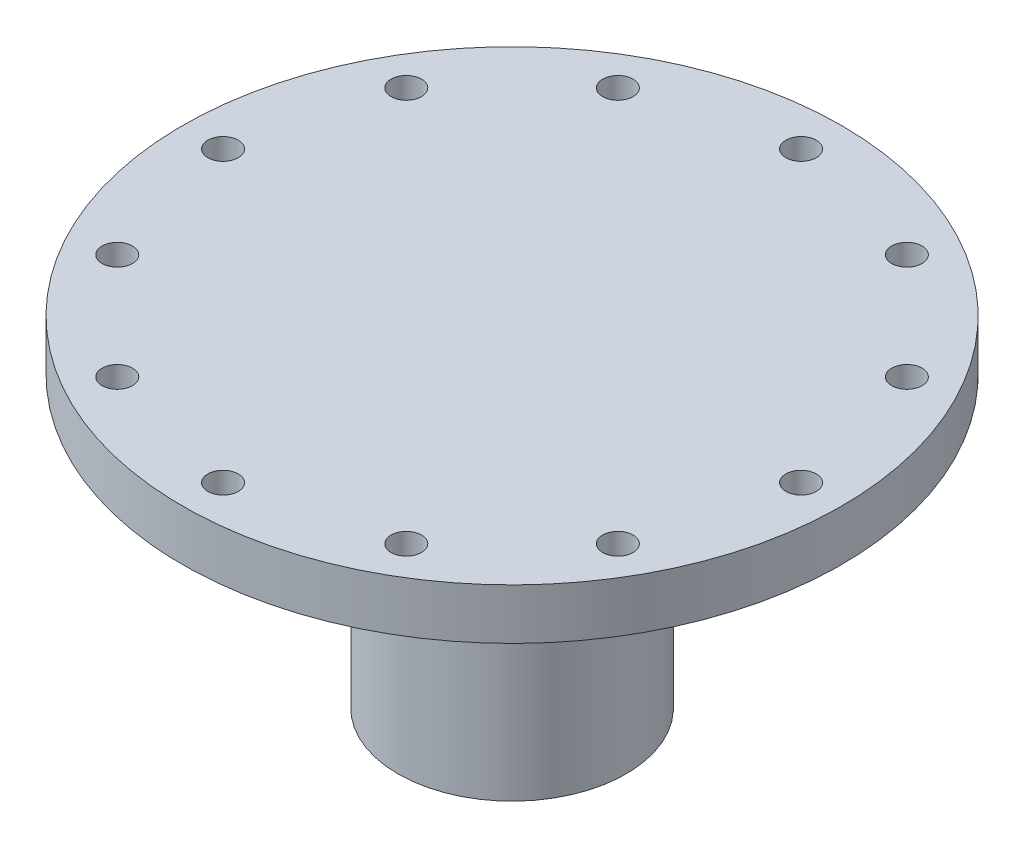
SolidWorks part; units mm, degrees
ref_plane "Front Plane" through (0, 0, 0) normal (0, 0, 1) x (1, 0, 0)
ref_plane "Top Plane" through (0, 0, 0) normal (0, 1, 0) x (1, 0, 0)
ref_plane "Right Plane" through (0, 0, 0) normal (1, 0, 0) x (0, 0, -1)
sketch "Sketch1" plane through (0, 0, 0) normal (1, 0, 0) x (0, 0, -1)
  line L0 (0, 0) -> (0, -47)
  line L1 (0, -47) -> (22.5, -47)
  line L2 (22.5, -47) -> (22.5, 0)
  line L3 (22.5, 0) -> (50, 0)
  line L4 (50, 0) -> (50, 20)
  line L5 (50, 20) -> (0, 20)
  line L6 (0, 20) -> (0, 0)
  dimension "D1" = 22.5
  dimension "D2" = 50
  dimension "D3" = 20
  dimension "D4" = 47
revolve "Revolve1" add sketch "Sketch1" angle 360 about L6
sketch "Sketch2" plane through (0, 0, 0) normal (0, 1, 0) x (1, 0, 0)
  line L0 (0, 0) -> (0, -57) construction
  circle A0 centre (0, 0) radius 65
  circle A1 centre (0, -57) radius 3
  circle A5 centre (-28.5, -49.3634) radius 3
  circle A6 centre (-49.3634, -28.5) radius 3
  circle A7 centre (-57, 0) radius 3
  circle A8 centre (-49.3634, 28.5) radius 3
  circle A9 centre (-28.5, 49.3634) radius 3
  circle A10 centre (0, 57) radius 3
  circle A11 centre (28.5, 49.3634) radius 3
  circle A12 centre (49.3634, 28.5) radius 3
  circle A13 centre (57, 0) radius 3
  circle A14 centre (49.3634, -28.5) radius 3
  circle A15 centre (28.5, -49.3634) radius 3
  point P29 (0, 0)
  dimension "D1" = 6
  dimension "D3" = 130
  dimension "D2" = 57
  dimension "D4" = 12
extrude "Boss-Extrude1" add sketch "Sketch2" against normal blind 10 from surface starting at face at (0, 20, 50)
